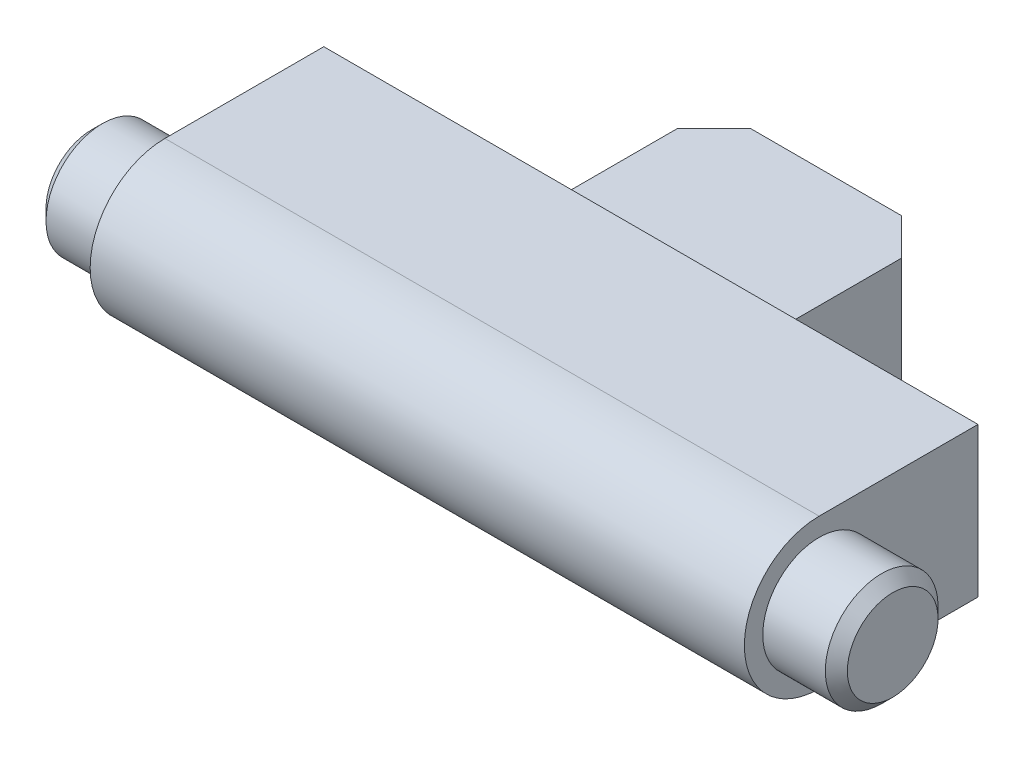
SolidWorks part; units mm, degrees
material "PET"
ref_plane "Front Plane" through (0, 0, 0) normal (0, 0, 1) x (1, 0, 0)
ref_plane "Top Plane" through (0, 0, 0) normal (0, 1, 0) x (1, 0, 0)
ref_plane "Right Plane" through (0, 0, 0) normal (1, 0, 0) x (0, 0, -1)
sketch "Sketch1" plane through (0, 0, 0) normal (0, 0, 1) x (1, 0, 0)
  line L0 (-610.9485, 499.4783) -> (-610.9485, 503.5423) construction
  line L6 (-614.1235, 499.4783) -> (-607.7735, 499.4783) construction
  line L9 (-619.8385, 499.4783) -> (-602.0585, 499.4783)
  line L10 (-619.8385, 499.4783) -> (-619.8385, 503.5423)
  line L11 (-619.8385, 503.5423) -> (-602.0585, 503.5423)
  line L12 (-602.0585, 499.4783) -> (-602.0585, 503.5423)
  line L13 (-619.8385, 499.4783) -> (-602.0585, 503.5423) construction
  line L14 (-619.8385, 503.5423) -> (-602.0585, 499.4783) construction
  point P8 (-610.9485, 501.5103)
  point P13 (0, 0)
  dimension "D1" = 17.78
  dimension "D2" = 4.064
extrude "Boss-Extrude1" add sketch "Sketch1" along normal blind 6.35
fillet "Fillet1" 2 edges at (-610.9485, 503.5423, 6.35) (-610.9485, 499.4783, 6.35) type full round first side face at (-610.9485, 503.5423, 3.175) second side face at (-610.9485, 499.4783, 3.175) middle face at (-610.9485, 501.5103, 6.35)
sketch "Sketch2" plane through (-619.8385, 0, 0) normal (-1, 0, 0) x (0, 0, 1)
  arc A2 (4.318, 499.9783) -> (4.318, 503.0423) centre (4.318, 501.5103) ccw
  circle A3 centre (4.318, 501.5103) radius 1.532
  point P0 (4.0967, 503.0423)
  dimension "D1" = 0.5
extrude "Boss-Extrude2" add sketch "Sketch2" along normal blind 2
chamfer "Chamfer1" distance 0.3 angle 45 1 edges at (-621.8385, 499.9783, 4.318)
ref_plane "Plane4" through (-610.9485, 0, 0) normal (-1, 0, 0) x (0, 0, 1)
mirror "Mirror1" about plane through (-610.9485, 0, 0) normal (-1, 0, 0) of "Chamfer1", "Boss-Extrude2"
sketch "Sketch3" plane through (0, 0, 0) normal (0, 0, -1) x (-1, 0, 0)
  line L8 (607.9005, 499.6053) -> (613.9965, 499.6053)
  line L9 (607.9005, 502.6533) -> (607.9005, 499.6053)
  line L10 (613.9965, 502.6533) -> (607.9005, 502.6533)
  line L11 (613.9965, 499.6053) -> (613.9965, 502.6533)
  line L12 (607.9005, 499.6053) -> (613.9965, 499.6053)
  line L13 (607.9005, 502.6533) -> (607.9005, 499.6053)
  line L14 (613.9965, 502.6533) -> (607.9005, 502.6533)
  line L15 (613.9965, 499.6053) -> (613.9965, 502.6533)
  dimension "D1" = 0.127
extrude "Boss-Extrude3" add sketch "Sketch3" along normal blind 4.7625
sketch "Sketch4" plane through (0, 499.6053, 0) normal (0, -1, 0) x (1, 0, 0)
  line L4 (-607.9005, 0) -> (-613.9965, 0)
  line L5 (-613.9965, 0) -> (-613.9965, -4.7625)
  line L6 (-613.9965, -4.7625) -> (-607.9005, -4.7625)
  line L7 (-607.9005, -4.7625) -> (-607.9005, 0)
  line L8 (-607.9005, 0) -> (-613.9965, 0)
  line L9 (-613.9965, 0) -> (-613.9965, -4.7625)
  line L10 (-613.9965, -4.7625) -> (-607.9005, -4.7625)
  line L11 (-607.9005, -4.7625) -> (-607.9005, 0)
  dimension "D1" = 0
extrude "Boss-Extrude4" add sketch "Sketch4" along normal up to surface (0.127 mm away) up to face at (-610.9485, 499.4783, 2.159)
chamfer "Chamfer2" distance 1 angle 45 2 edges at (-613.9965, 501.0658, -4.7625) (-607.9005, 501.0658, -4.7625)
